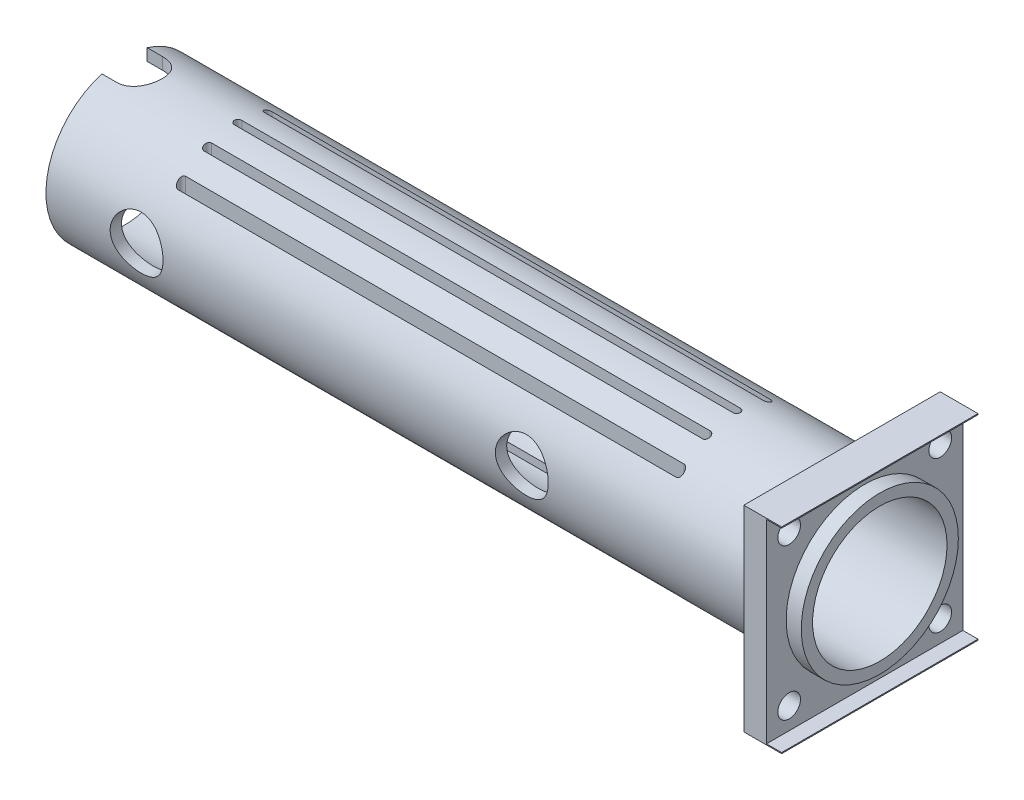
SolidWorks part; units mm, degrees
ref_plane "前视基准面" through (0, 0, 0) normal (0, 0, 1) x (1, 0, 0)
ref_plane "上视基准面" through (0, 0, 0) normal (0, 1, 0) x (1, 0, 0)
ref_plane "右视基准面" through (0, 0, 0) normal (1, 0, 0) x (0, 0, -1)
sketch "草图1" plane through (0, 0, 0) normal (0, 1, 0) x (1, 0, 0)
  line L0 (-93.5897, 0) -> (138.4615, 0) construction
  line L1 (0, 0) -> (100, 0)
  dimension "D1" = 100
sketch "草图2" plane through (0, 0, 0) normal (1, 0, 0) x (0, 0, -1)
  line L1 (-13, 13) -> (13, 13)
  line L2 (-13, 13) -> (-13, -13)
  line L3 (-13, -13) -> (13, -13)
  line L4 (13, 13) -> (13, -13)
  line L5 (0, -13) -> (0, 13) construction
  line L6 (-13, 0) -> (13, 0) construction
  circle A0 centre (0, 0) radius 8.9
  point P0 (0, 0)
  dimension "D1" = 26
  dimension "D2" = 26
sweep "枪管1" add profiles "草图2" path "草图1"
sketch "草图3" plane through (0, 0, 0) normal (1, 0, 0) x (0, 0, -1)
  line L1 (-16.7075, 15.4975) -> (16.7075, 15.4975)
  line L2 (-16.7075, 15.4975) -> (-16.7075, -15.4975)
  line L3 (-16.7075, -15.4975) -> (16.7075, -15.4975)
  line L4 (16.7075, 15.4975) -> (16.7075, -15.4975)
  line L5 (0, -15.4975) -> (0, 15.4975) construction
  line L6 (-16.7075, 0) -> (16.7075, 0) construction
  circle A0 centre (0, 0) radius 10.4
  point P0 (0, 0)
extrude "枪管2" cut sketch "草图3" along normal blind 95
ref_plane "基准面1" through (100, 0, 0) normal (1, 0, 0) x (0, 0, -1)
sketch "草图4" plane through (100, 0, 0) normal (1, 0, 0) x (0, 0, -1)
  line L1 (-13.5537, 12.8624) -> (13.5537, 12.8624)
  line L2 (-13.5537, 12.8624) -> (-13.5537, -12.8624)
  line L3 (-13.5537, -12.8624) -> (13.5537, -12.8624)
  line L4 (13.5537, 12.8624) -> (13.5537, -12.8624)
  line L5 (0, -12.8624) -> (0, 12.8624) construction
  line L6 (-13.5537, 0) -> (13.5537, 0) construction
  circle A0 centre (0, 0) radius 10.4
  point P0 (0, 0)
extrude "枪管3" cut sketch "草图4" against normal blind 2
sketch "草图5" plane through (0, 0, 0) normal (0, 0, 1) x (1, 0, 0)
  line L0 (-22.7608, 0) -> (113.9318, 0) construction
  circle A0 centre (12, 0) radius 3.5
  circle A1 centre (63, 0) radius 3.5
  dimension "D1" = 51
  dimension "D2" = 12
extrude "测速口" cut sketch "草图5" against normal through all and the other way through all
sketch "草图6" plane through (0, 0, 0) normal (0, 1, 0) x (1, 0, 0)
  line L0 (-18.3463, 0) -> (125.8352, 0) construction
  line L1 (-2, 0) -> (2, 0) construction
  line L2 (-2, 3) -> (2, 3)
  line L3 (-2, -3) -> (2, -3)
  arc A0 (-2, 3) -> (-2, -3) centre (-2, 0) ccw
  arc A1 (2, -3) -> (2, 3) centre (2, 0) ccw
  point P5 (0, 0)
  dimension "D1" = 4
  dimension "D2" = 3
extrude "枪口U型口" cut sketch "草图6" along normal through all
sketch "草图7" plane through (0, 0, 0) normal (0, 1, 0) x (1, 0, 0)
  line L0 (-21.8937, 0) -> (117.9876, 0) construction
  line L1 (48.047, -15.2678) -> (48.047, 27.7151) construction
  line L2 (12.0046, 4) -> (80.7632, 4) construction
  line L3 (12.0046, 7.4663) -> (80.7632, 7.4663) construction
  line L4 (12.0046, -4) -> (80.7632, -4) construction
  line L5 (12.0046, -7.4663) -> (80.7632, -7.4663) construction
  line L6 (15.047, 0) -> (81.047, 0) construction
  line L7 (15.047, 0.5) -> (81.047, 0.5)
  line L8 (15.047, -0.5) -> (81.047, -0.5)
  line L9 (15.047, -4) -> (81.047, -4) construction
  line L10 (15.047, -3.5) -> (81.047, -3.5)
  line L11 (15.047, -4.5) -> (81.047, -4.5)
  line L12 (15.047, -7.4663) -> (81.047, -7.4663) construction
  line L13 (15.047, -6.9663) -> (81.047, -6.9663)
  line L14 (15.047, -7.9663) -> (81.047, -7.9663)
  line L15 (15.047, 4) -> (81.047, 4) construction
  line L16 (15.047, 3.5) -> (81.047, 3.5)
  line L17 (15.047, 4.5) -> (81.047, 4.5)
  line L18 (15.047, 7.4663) -> (81.047, 7.4663) construction
  line L19 (15.047, 6.9663) -> (81.047, 6.9663)
  line L20 (15.047, 7.9663) -> (81.047, 7.9663)
  arc A0 (15.047, 0.5) -> (15.047, -0.5) centre (15.047, 0) ccw
  arc A1 (81.047, -0.5) -> (81.047, 0.5) centre (81.047, 0) ccw
  arc A2 (15.047, -3.5) -> (15.047, -4.5) centre (15.047, -4) ccw
  arc A3 (81.047, -4.5) -> (81.047, -3.5) centre (81.047, -4) ccw
  arc A4 (15.047, -6.9663) -> (15.047, -7.9663) centre (15.047, -7.4663) ccw
  arc A5 (81.047, -7.9663) -> (81.047, -6.9663) centre (81.047, -7.4663) ccw
  arc A6 (15.047, 3.5) -> (15.047, 4.5) centre (15.047, 4) cw
  arc A7 (81.047, 4.5) -> (81.047, 3.5) centre (81.047, 4) cw
  arc A8 (15.047, 6.9663) -> (15.047, 7.9663) centre (15.047, 7.4663) cw
  arc A9 (81.047, 7.9663) -> (81.047, 6.9663) centre (81.047, 7.4663) cw
  point P15 (48.047, 0)
  point P21 (48.047, -4)
  point P28 (48.047, -7.4663)
  point P34 (0, 0)
  point P37 (48.047, 4)
  point P44 (48.047, 7.4663)
  dimension "D3" = 66
  dimension "D1" = 4
  dimension "D2" = 3.4663
  dimension "D4" = 66
  dimension "D5" = 66
  dimension "D6" = 1
  dimension "D7" = 1
  dimension "D8" = 1
extrude "枪管镂空" cut sketch "草图7" against normal through all and the other way through all
sketch "草图9" plane through (100, 0, 0) normal (1, 0, 0) x (0, 0, -1)
  line L0 (-13.5795, 0) -> (15.2803, 0) construction
  line L1 (0, 12.9163) -> (0, -13.3143) construction
  circle A0 centre (-10, 10) radius 1.5
  circle A1 centre (10, 10) radius 1.5
  circle A2 centre (10, -10) radius 1.5
  circle A3 centre (-10, -10) radius 1.5
  dimension "D1" = 10
  dimension "D2" = 10
extrude "枪管固定口" cut sketch "草图9" against normal through all
cosmetic thread "装饰螺纹线1" parameters "D2"=9
cosmetic thread "装饰螺纹线2" parameters "D2"=9
